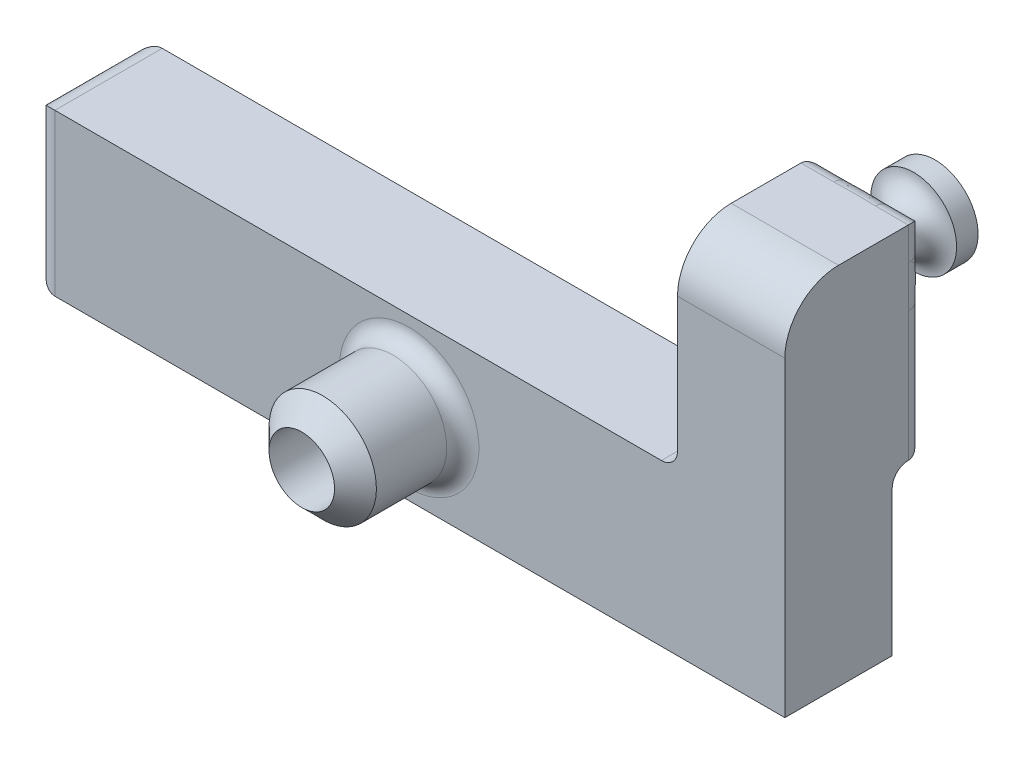
SolidWorks part; units mm, degrees
ref_plane "Front Plane" through (0, 0, 0) normal (0, 0, 1) x (1, 0, 0)
ref_plane "Top Plane" through (0, 0, 0) normal (0, 1, 0) x (1, 0, 0)
ref_plane "Right Plane" through (0, 0, 0) normal (1, 0, 0) x (0, 0, -1)
sketch "Sketch1" plane through (0, 0, 0) normal (0, 0, 1) x (1, 0, 0)
  line L0 (-35, -7.5) -> (35, -7.5)
  line L1 (-35, -7.5) -> (-35, 7.5)
  line L2 (35, -7.5) -> (35, 7.5)
  line L3 (-35, 7.5) -> (35, 7.5)
  line L4 (-35, -7.5) -> (35, 7.5) construction
  line L5 (35, -7.5) -> (-35, 7.5) construction
  circle A0 centre (0, 0) radius 3.05
  point P1 (0, 0)
  dimension "D3" = 6.1
  dimension "D1" = 70
  dimension "D2" = 15
  dimension "D4" = 35
extrude "Boss-Extrude1" add sketch "Sketch1" along normal blind 10
sketch "Sketch5" plane through (0, 0, 0) normal (0, 0, -1) x (-1, 0, 0)
  line L0 (-35, 26.5) -> (-25, 26.5)
  line L1 (-35, 26.5) -> (-35, 7.5)
  line L2 (-25, 26.5) -> (-25, 7.5)
  line L3 (-35, 7.5) -> (-25, 7.5)
  line L7 (-35, 7.5) -> (35, 7.5) construction
  line L8 (-35, -7.5) -> (-35, 7.5) construction
  dimension "D1" = 10
  dimension "D2" = 19
extrude "Boss-Extrude5" add sketch "Sketch5" against normal blind 10 and the other way blind 3 separate body
sketch "Sketch2" plane through (0, 0, 10) normal (0, 0, 1) x (1, 0, 0)
  line L0 (-35, 7.5) -> (-25, 7.5)
  line L1 (-35, 7.5) -> (-35, 17.5)
  line L2 (-25, 7.5) -> (-25, 17.5)
  line L3 (-35, 17.5) -> (-25, 17.5)
  line L4 (35, 7.5) -> (-35, 7.5) construction
  dimension "D1" = 10
  dimension "D2" = 10
extrude "Boss-Extrude2" [suppressed] add sketch "Sketch2" against normal blind 10
sketch "Sketch3" plane through (-35, 0, -3) normal (0, 0, -1) x (-1, 0, 0)
  line L0 (-70, -7.5) -> (-70, 7.5) construction
  line L1 (-60, 7.5) -> (-60, 26.5) construction
  line L2 (-60, 26.5) -> (-70, 26.5) construction
  circle A0 centre (-65, 21.5) radius 2
  point P9 (-60, 17)
  dimension "D1" = 4
  dimension "D2" = 5
  dimension "D3" = 5
fillet "Fillet1" radius 2 4 edges at (-35, 0, 0) (-35, -7.5, 5) (-35, 0, 10) (-35, 7.5, 5)
extrude "Boss-Extrude6" add sketch "Sketch3" along normal blind 4
sketch "Sketch6" plane through (0, 0, -7) normal (0, 0, -1) x (-1, 0, 0)
  circle A2 centre (-30, 21.5) radius 4
  circle A3 centre (-30, 21.5) radius 4
  dimension "D1" = 2
extrude "Boss-Extrude7" add sketch "Sketch6" along normal blind 2
fillet "Fillet4" radius 5 1 edges at (30, 26.5, 10)
combine bodies "Combine1" operation type add bodies to combine 106 105 107 101
fillet "Fillet7" radius 2 2 edges at (28, 21.5, -7) (28, 21.5, -3)
fillet "Fillet3" radius 1.5 5 edges at (30, 7.5, -3) (30, 7.5, 0) (25, 17, -3) (30, 26.5, -3) (35, 17, -3)
fillet "Fillet9" radius 1.5 2 edges at (25, 6.75, 0) (25, 7.5, 5)
sketch "Sketch8" plane through (0, 0, 0) normal (1, 0, 0) x (0, 0, -1)
  line L0 (-10, 0) -> (-20, 0)
  line L1 (-10, 21.5) -> (-10, -7.5) construction
  line L2 (-20, 0) -> (-20, 3.05)
  line L3 (-20, 3.05) -> (-18.05, 5)
  line L4 (-18.05, 5) -> (-10, 5)
  line L5 (-10, 5) -> (-10, 0)
  dimension "D1" = 3.05
  dimension "D2" = 5
  dimension "D3" = 10
  dimension "D4" = 135
revolve "Revolve1" add sketch "Sketch8" angle 360 about L0
sketch "Sketch9" plane through (0, 0, 10) normal (0, 0, -1) x (-1, 0, 0)
  circle A1 centre (0, 0) radius 3.05
  circle A2 centre (0, 0) radius 3.05
  dimension "D1" = 0
extrude "Cut-Extrude1" cut sketch "Sketch9" against normal blind 10
fillet "Fillet10" radius 1.5 1 edges at (0, 5, 10)
sketch "Sketch10" plane through (0, 0, 0) normal (0, 0, -1) x (-1, 0, 0)
  line L1 (33, -7.5) -> (-35, -7.5) construction
  line L2 (-35, -7.5) -> (-35, 6) construction
  line L3 (-35, -5.5) -> (-35, -7.5)
  line L4 (-35, -7.5) -> (-15, -7.5)
  arc A0 (-15, -7.5) -> (-35, -5.5) centre (-15, 93.5) cw
  dimension "D2" = 2
  dimension "D1" = 20
extrude "Cut-Extrude2" [suppressed] cut sketch "Sketch10" against normal blind 10
